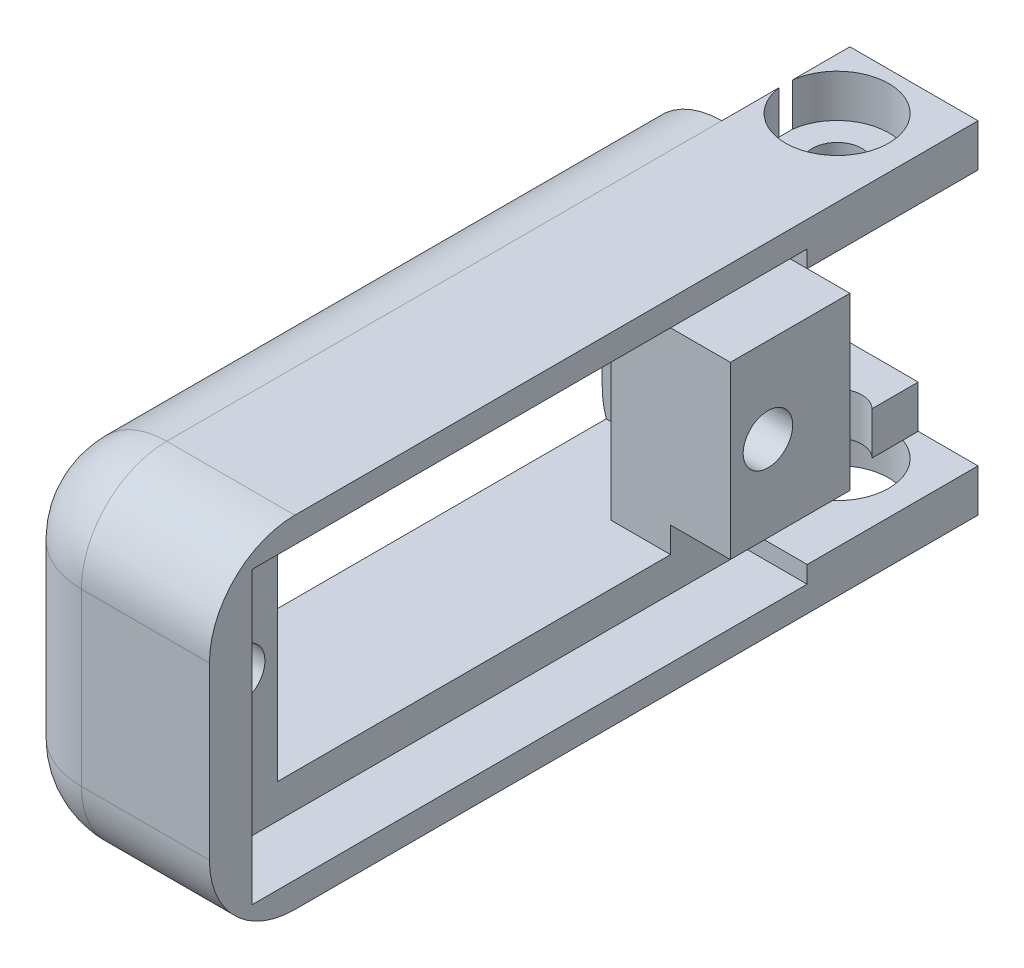
SolidWorks part; units mm, degrees
ref_plane "Спереди" through (0, 0, 0) normal (0, 0, 1) x (1, 0, 0)
ref_plane "Сверху" through (0, 0, 0) normal (0, 1, 0) x (1, 0, 0)
ref_plane "Справа" through (0, 0, 0) normal (1, 0, 0) x (0, 0, -1)
sketch "Эскиз1" plane through (0, 0, 0) normal (0, 1, 0) x (1, 0, 0)
  line L1 (-12.5, -18.75) -> (12.5, -18.75)
  line L2 (-12.5, -18.75) -> (-12.5, 18.75)
  line L3 (-12.5, 18.75) -> (12.5, 18.75)
  line L4 (12.5, -18.75) -> (12.5, 18.75)
  line L5 (-12.5, -18.75) -> (12.5, 18.75) construction
  line L6 (-12.5, 18.75) -> (12.5, -18.75) construction
  point P0 (0, 0)
  dimension "D1" = 37.5
  dimension "D2" = 25
extrude "Бобышка-Вытянуть1" add sketch "Эскиз1" along normal blind 20
fillet "Скругление1" radius 5 8 edges at (-12.5, 10, 18.75) (0, 20, 18.75) (12.5, 10, 18.75) (0, 0, 18.75) (12.5, 20, 0) (12.5, 0, 0) (-12.5, 0, 0) (-12.5, 20, 0)
sketch "Эскиз2" plane through (0, 20, 0) normal (0, 1, 0) x (1, 0, 0)
  line L0 (7.5, 18.75) -> (-7.5, 18.75) construction
  line L1 (-7.5, 18.75) -> (7.5, 18.75)
  line L2 (-7.5, 18.75) -> (-7.5, 26.25)
  line L3 (-7.5, 26.25) -> (7.5, 26.25)
  line L4 (7.5, 18.75) -> (7.5, 26.25)
  point P6 (0, 26.25)
  dimension "D1" = 7.5
  dimension "D2" = 15
extrude "Бобышка-Вытянуть2" add sketch "Эскиз2" against normal blind 5
extrude "Бобышка-Вытянуть3" add sketch "Эскиз2<2>" along normal blind 5 from surface starting at face at (0, 0, -2.5)
sketch "Эскиз2<2>" plane through (0, 20, 0) normal (0, 1, 0) x (1, 0, 0) same geometry as "Эскиз2"
sketch "Эскиз3" plane through (0, 20, 0) normal (0, 1, 0) x (1, 0, 0)
  line L0 (-1007.5, 22.5) -> (48992.5, 22.5) construction
  line L1 (-7.5, 26.25) -> (-7.5, 18.75) construction
  line L2 (7.5, 18.75) -> (7.5, 26.25) construction
  circle A0 centre (-4.5, 22.5) radius 1.45
  circle A1 centre (4.5, 22.5) radius 1.45
  point P5 (-7.5, 22.5)
  dimension "D1" = 2.9
  dimension "D3" = 3
  dimension "D2" = 3
extrude "Вырез-Вытянуть1" cut sketch "Эскиз3" against normal blind 20
sketch "Эскиз4" plane through (0, 20, 0) normal (0, 1, 0) x (1, 0, 0)
  circle A0 centre (-4.5, 22.5) radius 3.025
  circle A1 centre (4.5, 22.5) radius 3.025
  dimension "D1" = 6.05
extrude "Вырез-Вытянуть3" cut sketch "Эскиз4" against normal blind 2.5
extrude "Вырез-Вытянуть4" cut sketch "Эскиз4<2>" along normal blind 2.5 from surface starting at face at (-4.5, 0, -21.05)
sketch "Эскиз4<2>" plane through (0, 20, 0) normal (0, 1, 0) x (1, 0, 0) same geometry as "Эскиз4"
sketch "Эскиз5" plane through (-12.5, 0, 0) normal (-1, 0, 0) x (0, 0, 1)
  line L0 (-18.75, 15) -> (-18.75, 5) construction
  line L1 (-16.75, 16.5) -> (16.25, 16.5)
  line L2 (-16.75, 16.5) -> (-16.75, 3.5)
  line L3 (-16.75, 3.5) -> (16.25, 3.5)
  line L4 (16.25, 16.5) -> (16.25, 3.5)
  line L5 (-1020, 10) -> (48980, 10) construction
  point P7 (-16.75, 10)
  point P9 (-18.75, 10)
  dimension "D1" = 33
  dimension "D2" = 2
  dimension "D3" = 13
extrude "Вырез-Вытянуть5" cut sketch "Эскиз5" against normal blind 5.5
sketch "Эскиз6" plane through (-7, 0, 0) normal (-1, 0, 0) x (0, 0, 1)
  line L0 (13.75, 16.5) -> (-16.75, 16.5) construction
  line L1 (-11.75, 16.5) -> (11.25, 16.5)
  line L2 (-11.75, 16.5) -> (-11.75, 3.5)
  line L3 (-11.75, 3.5) -> (11.25, 3.5)
  line L4 (11.25, 16.5) -> (11.25, 3.5)
  line L5 (-16.75, 3.5) -> (13.75, 3.5) construction
  line L6 (-0.25, -983.5) -> (-0.25, 49016.5) construction
  line L7 (16.25, 16.5) -> (-16.75, 16.5) construction
  point P8 (-0.25, 16.5)
  point P16 (-0.25, 16.5)
  dimension "D1" = 23
extrude "Вырез-Вытянуть6" cut sketch "Эскиз6" against normal blind 18.5
sketch "Эскиз7" plane through (-7, 0, 0) normal (-1, 0, 0) x (0, 0, 1)
  line L0 (-0.25, -983.5) -> (-0.25, 49016.5) construction
  line L2 (-1020, 10) -> (48980, 10) construction
  line L3 (-18.75, 15) -> (-18.75, 5) construction
  line L4 (11.25, 16.5) -> (-11.75, 16.5) construction
  circle A0 centre (-13.95, 10) radius 1.45
  circle A1 centre (13.45, 10) radius 1.45
  point P7 (-0.25, 16.5)
  point P14 (-18.75, 10)
  dimension "D1" = 27.4
  dimension "D2" = 2.9
extrude "Вырез-Вытянуть7" cut sketch "Эскиз7" against normal blind 14.5
sketch "Эскиз8" plane through (0, 0, -26.25) normal (0, 0, -1) x (-1, 0, 0)
  line L0 (7.5, 15) -> (-7.5, 15) construction
  line L1 (-3.5, 15) -> (3.5, 15)
  line L2 (-3.5, 15) -> (-3.5, 17.5)
  line L3 (-3.5, 17.5) -> (3.5, 17.5)
  line L4 (3.5, 15) -> (3.5, 17.5)
  line L5 (-1012.5, 10) -> (48987.5, 10) construction
  line L6 (-12.5, 15) -> (-12.5, 5) construction
  line L7 (3.5, 5) -> (3.5, 2.5)
  line L8 (-3.5, 2.5) -> (3.5, 2.5)
  line L9 (-3.5, 5) -> (-3.5, 2.5)
  line L10 (-3.5, 5) -> (3.5, 5)
  point P7 (0, 15)
  point P13 (-12.5, 10)
  dimension "D1" = 7
  dimension "D2" = 2.5
extrude "Вырез-Вытянуть8" cut sketch "Эскиз8" against normal blind 42.5
sketch "Эскиз9" plane through (0, 0, 11.25) normal (0, 0, -1) x (-1, 0, 0)
  line L1 (3.5, 17.5) -> (-8.5, 17.5)
  line L2 (3.5, 17.5) -> (3.5, 2.5)
  line L3 (3.5, 2.5) -> (-8.5, 2.5)
  line L4 (-8.5, 17.5) -> (-8.5, 2.5)
  line L5 (-3.5, 2.5) -> (3.5, 2.5) construction
  point P7 (3.5, 17.5)
  dimension "D1" = 12
extrude "Вырез-Вытянуть9" cut sketch "Эскиз9" against normal up to surface (5 mm away) up to face at (0, 16.25, 16.25)
sketch "Эскиз10" plane through (0, 17.5, 0) normal (0, -1, 0) x (1, 0, 0)
  line L0 (3.5, 11.25) -> (3.5, -19.6451) construction
  line L1 (-3.5, 16.25) -> (3.5, 16.25)
  line L2 (-3.5, 16.25) -> (-3.5, -16.25)
  line L3 (-3.5, -16.25) -> (3.5, -16.25)
  line L4 (3.5, 16.25) -> (3.5, -16.25)
  dimension "D1" = 32.5
extrude "Вырез-Вытянуть10" cut sketch "Эскиз10" against normal blind 1
extrude "Вырез-Вытянуть11" cut sketch "Эскиз10<2>" along normal blind 1 from surface starting at face at (1.7, 2.5, -8.75)
sketch "Эскиз10<2>" plane through (0, 17.5, 0) normal (0, -1, 0) x (1, 0, 0) same geometry as "Эскиз10"
sketch "Эскиз11" plane through (-7, 0, 0) normal (-1, 0, 0) x (0, 0, 1)
  circle A0 centre (-13.95, 10) radius 3
  circle A1 centre (13.45, 10) radius 3
  circle A2 centre (-13.95, 10) radius 1.45 construction
  dimension "D1" = 6
extrude "Вырез-Вытянуть12" cut sketch "Эскиз11" along normal up to surface (5.5 mm away) up to face at (-12.5, 10, -17.75)
sketch "Эскиз12" plane through (12.5, 0, 0) normal (1, 0, 0) x (0, 0, -1)
  circle A0 centre (-4.87, 10) radius 4
  circle A1 centre (-13.45, 10) radius 1.45 construction
  circle A2 centre (-13.45, 10) radius 1.45 construction
  point P5 (0, 0)
  dimension "D1" = 8.58
  dimension "D2" = 8
extrude "Бобышка-Вытянуть4" add sketch "Эскиз12" along normal blind 5
sketch "Эскиз13" plane through (0, 20, 0) normal (0, 1, 0) x (1, 0, 0)
  line L0 (7.5, 26.25) -> (-7.5, 26.25) construction
  line L1 (0, 26.25) -> (22.0838, 26.25)
  line L2 (0, 26.25) -> (0, -21.0108)
  line L3 (0, -21.0108) -> (22.0838, -21.0108)
  line L4 (22.0838, 26.25) -> (22.0838, -21.0108)
extrude "Вырез-Вытянуть13" cut sketch "Эскиз13" against normal blind 23
